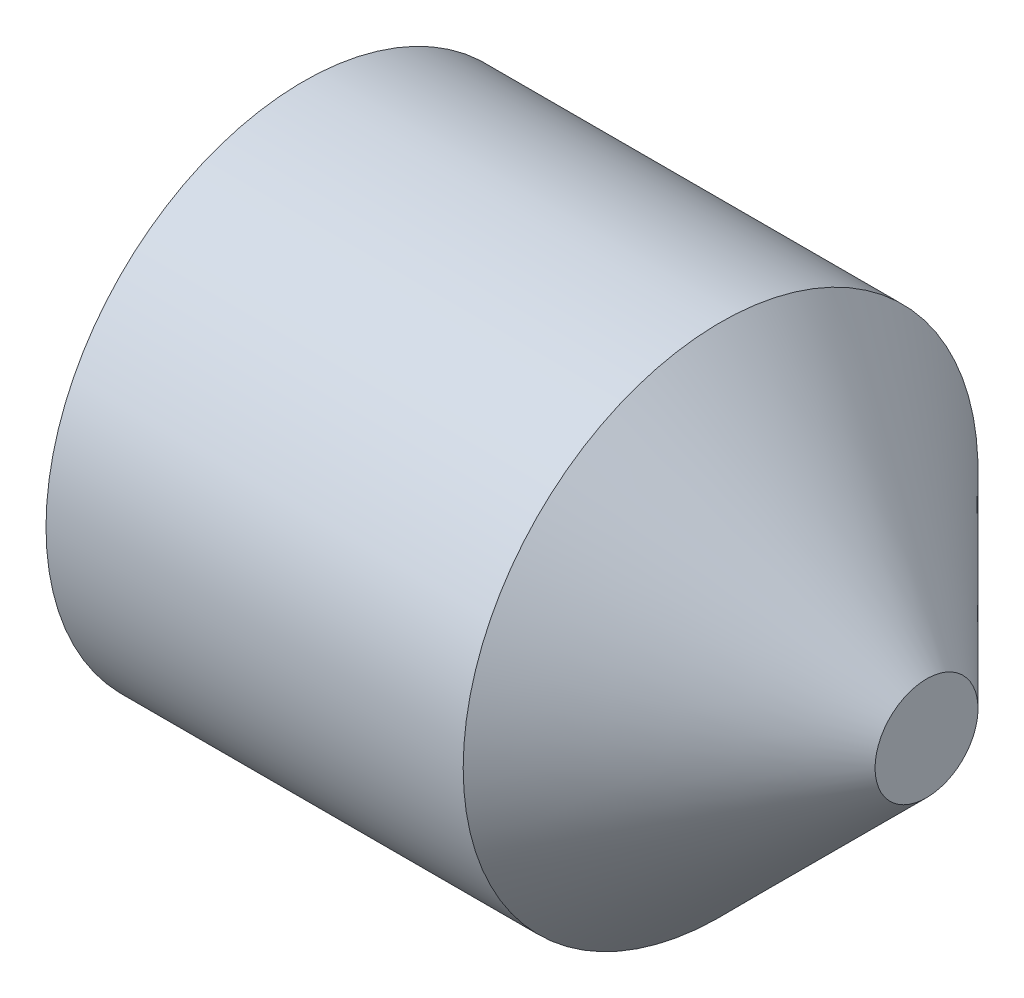
SolidWorks part; units mm, degrees
revolve "BaseBody" add sketch "BodySke" angle 360 about L5 other way angle 60
sketch "BodySke" plane through (0, 0, 0) normal (0, 0, 1) x (1, 0, 0)
  line L0 (0, 0) -> (0, 10.352)
  line L1 (0, 10.352) -> (0.9515, 12)
  line L2 (0.9515, 12) -> (20.4, 12)
  line L3 (30, 0) -> (30, 2.4)
  line L4 (30, 0) -> (0, 0)
  line L5 (-12.7, 0) -> (88.9, 0) construction
  line L6 (30, 2.4) -> (20.4, 12)
  line L7 (3, 15.875) -> (3, -3.175) construction
  line L8 (0, -10.352) -> (0.9515, -12) construction
  line L9 (30, -2.4) -> (20.4, -12) construction
  dimension "Length" = 30
  dimension "Tip_dia" = 4.8
  dimension "Cone_ang" = 90
  dimension "Diameter" = 24
cosmetic thread "ThreadCosmetic" [suppressed] parameters "Thread_minor"=20.704
ref_plane "Plane1" through (0, 0, 0) normal (0, 0, 1) x (1, 0, 0)
ref_plane "Plane2" through (0, 0, 0) normal (0, 1, 0) x (1, 0, 0)
ref_plane "Plane3" through (0, 0, 0) normal (1, 0, 0) x (0, 0, -1)
sketch "Sketch2" plane through (0, 0, 0) normal (-1, 0, 0) x (0, 0, 1)
  line L0 (3.4641, 6) -> (-3.4641, 6)
  line L1 (-3.4641, 6) -> (-6.9282, 0)
  line L2 (3.4641, 6) -> (6.9282, 0)
  line L3 (3.4641, -6) -> (6.9282, 0)
  line L4 (3.4641, -6) -> (-3.4641, -6)
  line L5 (-3.4641, -6) -> (-6.9282, 0)
  dimension "D2" = 6
  dimension "D3" = 6
extrude "Hex" cut sketch "Sketch2" against normal blind 10
sketch "Sketch4" plane through (0, 4.7709, -0.5249) normal (-1, 0, 0) x (0, 0, 1)
  line L0 (0.5249, -4.7709) -> (10.6976, -4.7709)
  line L1 (0.5249, -4.7709) -> (6.6732, -1.2211) construction
  line L2 (0.5249, -4.7709) -> (5.6112, 4.0389)
  line L3 (8.9666, -2.6687) -> (10.2861, -1.9069)
  line L4 (6.5663, 1.4888) -> (7.8858, 2.2506)
  arc A0 (8.9666, -2.6687) -> (6.5663, 1.4888) centre (0.5249, -4.7709) ccw
  arc A1 (10.6976, -4.7709) -> (10.2861, -1.9069) centre (0.5249, -4.7709) ccw
  arc A2 (5.6112, 4.0389) -> (7.8858, 2.2506) centre (0.5249, -4.7709) cw
  circle A3 centre (0.5249, -4.7709) radius 8.6995 construction
  circle A4 centre (0.5249, -4.7709) radius 10.1727 construction
  dimension "Spline_n_dim" = 17.399
  dimension "Spline_m_dim" = 20.3454
  dimension "D1" = 30
  dimension "Spline_p_dim" = 4.8006
  dimension "D3" = 2.4003
extrude "Spline6" [suppressed] cut sketch "Sketch4" against normal blind 12
pattern_circular "CirPattern1" [suppressed] count 6 every 60 about axis through (-12.7, 0, 0) along (1, 0, 0)
sketch "Sketch5" plane through (0, 1.4735, 6.925) normal (-1, 0, 0) x (0, 0, 1)
  line L0 (-6.925, -1.4735) -> (3.2477, -1.4735)
  line L1 (-6.925, -1.4735) -> (-1.9049, 3.5466) construction
  line L2 (-6.925, -1.4735) -> (-6.925, 8.6992)
  line L3 (0.9237, 2.9807) -> (1.7623, 3.8193)
  line L4 (-2.4708, 6.3752) -> (-1.6322, 7.2139)
  line L5 (-2.4708, 6.3752) -> (0.9237, 2.9807)
  arc A1 (3.2477, -1.4735) -> (1.7623, 3.8193) centre (-6.925, -1.4735) ccw
  arc A2 (-6.925, 8.6992) -> (-1.6322, 7.2139) centre (-6.925, -1.4735) cw
  circle A3 centre (-6.925, -1.4735) radius 8.6995 construction
  circle A4 centre (-6.925, -1.4735) radius 10.1727 construction
  dimension "Spline_n_dim" = 17.399
  dimension "Spline_m_dim" = 20.3454
  dimension "Spline_p_dim" = 4.8006
  dimension "D3" = 2.4003
  dimension "D1" = 45
  dimension "Spline_a_dim" = 90
extrude "Spline4" [suppressed] cut sketch "Sketch5" against normal blind 12
pattern_circular "CirPattern2" [suppressed] count 4 every 90 about axis through (-12.7, 0, 0) along (1, 0, 0)
sketch "ThdSchSke" plane through (0, 0, 0) normal (0, 0, 1) x (1, 0, 0)
  line L0 (0.9515, -10.352) -> (-0.2025, -12)
  line L1 (0.9515, -10.352) -> (2.1054, -12)
  line L2 (2.1054, -12) -> (2.1054, -15)
  line L3 (-3.175, 0) -> (5.1513, 0) construction
  line L4 (0.9515, 12) -> (0.9515, -12) construction
  line L5 (2.1054, -15) -> (-0.2025, -15)
  line L6 (-0.2025, -15) -> (-0.2025, -12)
  dimension "Thread_minor" = 20.704
  dimension "Diameter" = 24
revolve "ThreadSchematic" [suppressed] cut sketch "ThdSchSke" angle 360 about L3
pattern_linear "ThdSchPat" [suppressed]
equation "\"D2@Sketch2\" = \"Hex_size@Sketch2\" / 2"
equation "\"D3@Sketch2\" = \"Hex_size@Sketch2\" / 2"
equation "\"Thread_minor@ThreadCosmetic\" = \"Minor_dia@BodySke\""
equation "\"D1@Sketch4\" = \"Spline_a_dim@Sketch4\" / 2"
equation "\"D3@Sketch4\" = \"Spline_p_dim@Sketch4\" / 2"
equation "\"D2@CirPattern1\" = \"Spline_a_dim@Sketch4\""
equation "\"Num_teeth@CirPattern1\" = 360 / \"D2@CirPattern1\""
equation "\"Spline_a_dim@Sketch5\" = 90"
equation "\"Spline_p_dim@Sketch5\" = \"Spline_p_dim@Sketch4\""
equation "\"Spline_m_dim@Sketch5\" = \"Spline_m_dim@Sketch4\""
equation "\"Spline_n_dim@Sketch5\" = \"Spline_n_dim@Sketch4\""
equation "\"D1@Sketch5\" = \"Spline_a_dim@Sketch5\" / 2"
equation "\"D3@Sketch5\" = \"Spline_p_dim@Sketch5\" / 2"
equation "\"Key_eng@Spline4\" = \"Key_eng@Spline6\""
equation "\"Thread_minor@ThdSchSke\" = \"Thread_minor@ThreadCosmetic\""
equation "\"Diameter@ThdSchSke\" = \"Diameter@BodySke\""
equation "\"Overcut@ThdSchSke\" = \"Diameter@BodySke\" * 1.25"
equation "\"Num_threads@ThdSchPat\" = int( (\"Length@BodySke\" - ( ( ( \"Diameter@BodySke\" - \"Minor_dia@BodySke\" ) * 0.5 ) / tan( \"Drive_ch_ang@BodySke\" * 0.017453292 ) ) - ( ( \"Diameter@BodySke\" * 0.5 ) / tan( \"Cone_ang@BodySke\" * 0.008726646 ) ) ) / \"Advance@BodySke\" + 0.999 )  + 1"
equation "\"Num_threads@ThdSchPat\" = int( (\"Length@BodySke\" - ( ( ( \"Diameter@BodySke\" - \"Minor_dia@BodySke\" ) * 0.5 ) / tan( \"Drive_ch_ang@BodySke\" * 0.017453292 ) ) - ( (( \"Diameter@BodySke\" - \"Tip_dia@BodySke\") * 0.5 ) / tan( \"Cone_ang@BodySke\" * 0.008726646 ) ) ) / \"Advance@BodySke\" + 0.999 )  + 1"
equation "\"Advance@ThdSchPat\" = (\"Length@BodySke\" - ( ( ( \"Diameter@BodySke\" - \"Minor_dia@BodySke\" ) * 0.5 ) / tan( \"Drive_ch_ang@BodySke\" * 0.017453292 ) ) - ( ( \"Diameter@BodySke\" * 0.5 ) / tan( \"Cone_ang@BodySke\" * 0.008726646 ) ) ) /  (\"Num_threads@ThdSchPat\" - 1) 'relax it"
equation "\"Advance@ThdSchPat\" = (\"Length@BodySke\" - ( ( ( \"Diameter@BodySke\" - \"Minor_dia@BodySke\" ) * 0.5 ) / tan( \"Drive_ch_ang@BodySke\" * 0.017453292 ) ) - ( ( (\"Diameter@BodySke\" - \"Tip_dia@BodySke\") * 0.5 ) / tan( \"Cone_ang@BodySke\" * 0.008726646 ) ) ) /  (\"Num_threads@ThdSchPat\" - 1) 'relax it"
equation "' \"Num_threads@ThdSchPat\" = \"Num_threads@ThdSchPat\" - sgn( \"Num_threads@ThdSchPat\" - 1) '---chamfered tips only---"
